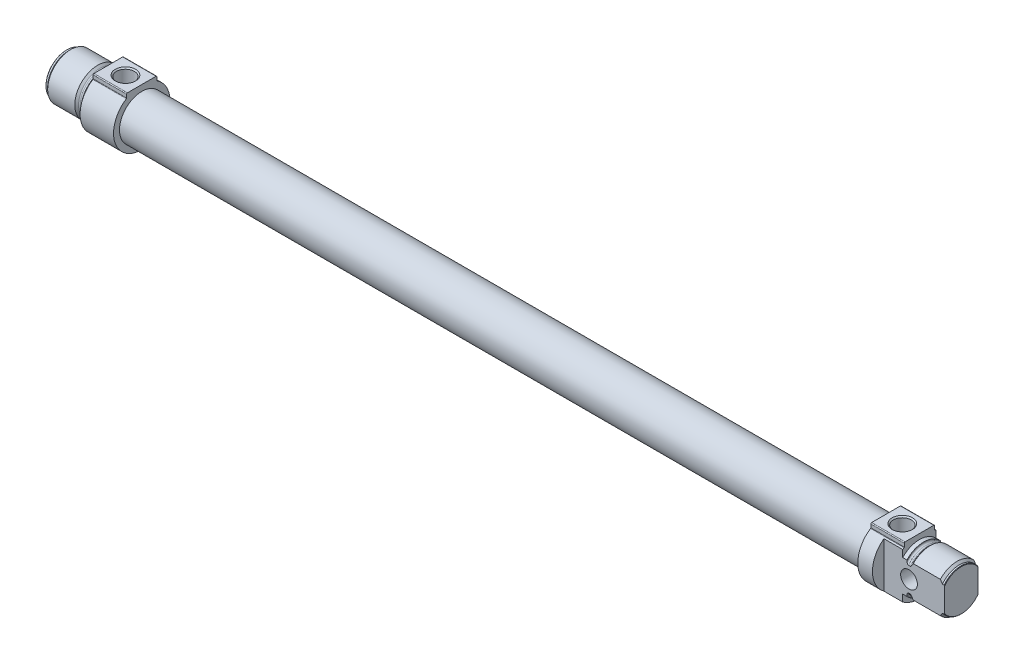
SolidWorks part; units mm, degrees
ref_plane "Ebene vorne" through (0, 0, 0) normal (0, 0, 1) x (1, 0, 0)
ref_plane "Ebene oben" through (0, 0, 0) normal (0, 1, 0) x (1, 0, 0)
ref_plane "Ebene rechts" through (0, 0, 0) normal (1, 0, 0) x (0, 0, -1)
sketch "Skizze1" plane through (0, 0, 0) normal (0, 0, 1) x (1, 0, 0)
  line L0 (0, 0) -> (0, 9.8)
  line L1 (0, 9.8) -> (0.2, 10)
  line L2 (0.2, 10) -> (1, 10)
  line L3 (1, 10) -> (2, 11)
  line L4 (2, 11) -> (14.95, 11)
  line L5 (14.95, 11) -> (15.8657, 10.0843)
  line L6 (16.4314, 9.85) -> (17.2, 9.85)
  line L7 (18, 10.65) -> (18, 11)
  line L8 (18, 11) -> (20, 11)
  line L9 (20, 11) -> (20, 0)
  line L10 (20, 0) -> (0, 0)
  line L11 (20, 0) -> (0, 0) construction
  arc A0 (15.8657, 10.0843) -> (16.4314, 9.85) centre (16.4314, 10.65) ccw
  arc A1 (17.2, 9.85) -> (18, 10.65) centre (17.2, 10.65) ccw
revolve "Rotation1" add sketch "Skizze1" angle 360 about L11 reverse direction yes
cosmetic thread "Gewindedarstellung1" parameters "D1"=13.87, "D2"=20.16
ref_plane "Ebene1" through (28.7, 0, 0) normal (1, 0, 0) x (0, 0, -1)
ref_plane "Ebene2" through (10.5, 0, 0) normal (1, 0, 0) x (0, 0, -1)
ref_plane "Ebene3" through (0, -14, 0) normal (0, 1, 0) x (1, 0, 0)
ref_plane "Ebene4" through (0, 13, 0) normal (0, 1, 0) x (1, 0, 0)
ref_plane "Ebene5" through (0, 0, 0) normal (0, 1, 0) x (1, 0, 0)
ref_plane "Ebene6" through (0, 0, 0) normal (0, 1, 0) x (1, 0, 0)
ref_plane "Ebene7" through (20, 0, 0) normal (1, 0, 0) x (0, 0, -1)
ref_plane "Ebene8" through (20, 0, 0) normal (1, 0, 0) x (0, 0, -1)
ref_plane "Ebene9" through (33, 0, 0) normal (1, 0, 0) x (0, 0, -1)
ref_plane "Ebene10" through (24.5, 0, 0) normal (1, 0, 0) x (0, 0, -1)
ref_plane "Ebene11" through (44.5, 0, 0) normal (1, 0, 0) x (0, 0, -1)
sketch "Skizze2" plane through (20, 0, 0) normal (1, 0, 0) x (0, 0, -1)
  line L0 (7.25, 11.5515) -> (7.25, 13.1)
  line L1 (6.85, 13.5) -> (-6.85, 13.5)
  line L2 (-7.25, 13.1) -> (-7.25, 11.5515)
  arc A0 (-7.3859, 11.3004) -> (7.3859, 11.3004) centre (0, 0) ccw
  arc A1 (7.3859, 11.3004) -> (7.25, 11.5515) centre (7.55, 11.5515) cw
  arc A2 (7.25, 13.1) -> (6.85, 13.5) centre (6.85, 13.1) ccw
  arc A3 (-6.85, 13.5) -> (-7.25, 13.1) centre (-6.85, 13.1) ccw
  arc A4 (-7.25, 11.5515) -> (-7.3859, 11.3004) centre (-7.55, 11.5515) cw
extrude "Aufsatz-Linear austragen1" add sketch "Skizze2" along normal blind 16
ref_plane "Ebene12" through (32.5, 0, 0) normal (1, 0, 0) x (0, 0, -1)
ref_plane "Ebene13" through (0, 0, 0) normal (0, 0, 1) x (1, 0, 0)
ref_plane "Ebene14" through (0, 0, -8.5) normal (0, 0, 1) x (1, 0, 0)
ref_plane "Ebene15" through (0, 0, 0) normal (0, 1, 0) x (1, 0, 0)
ref_plane "Ebene16" through (0, 6.9, 0) normal (0, 1, 0) x (1, 0, 0)
ref_plane "Ebene17" through (0, 0, -6.6) normal (0, 0, 1) x (1, 0, 0)
ref_plane "Ebene18" through (0, 0, 0) normal (0, 1, 0) x (1, 0, 0)
ref_plane "Ebene19" through (0, 6.9, 0) normal (0, 1, 0) x (1, 0, 0)
ref_plane "Ebene20" through (0, 7.8206, -1.379) normal (0, 0.9848, -0.1736) x (1, 0, 0)
ref_plane "Ebene21" through (0, 6.3434, -1.1185) normal (0, 0.9848, -0.1736) x (1, 0, 0)
sketch "Skizze3" plane through (0, 0, 0) normal (0, 0, 1) x (1, 0, 0)
  line L0 (36, 0) -> (36, 10.65)
  line L1 (36, 10.65) -> (392, 10.65)
  line L2 (392, 10.65) -> (392, 0)
  line L3 (392, 0) -> (36, 0)
  line L4 (392, 0) -> (36, 0) construction
revolve "Rotation2" add sketch "Skizze3" angle 360 about L4 reverse direction yes
ref_plane "Ebene22" through (392, 0, 0) normal (1, 0, 0) x (0, 0, -1)
sketch "Skizze4" plane through (392, 0, 0) normal (1, 0, 0) x (0, 0, -1)
  line L0 (7.25, 11.5515) -> (7.25, 13.1)
  line L1 (6.85, 13.5) -> (-6.85, 13.5)
  line L2 (-7.25, 13.1) -> (-7.25, 11.5515)
  arc A0 (-7.3859, 11.3004) -> (7.3859, 11.3004) centre (0, 0) ccw
  arc A1 (7.3859, 11.3004) -> (7.25, 11.5515) centre (7.55, 11.5515) cw
  arc A2 (7.25, 13.1) -> (6.85, 13.5) centre (6.85, 13.1) ccw
  arc A3 (-6.85, 13.5) -> (-7.25, 13.1) centre (-6.85, 13.1) ccw
  arc A4 (-7.25, 11.5515) -> (-7.3859, 11.3004) centre (-7.55, 11.5515) cw
extrude "Aufsatz-Linear austragen2" add sketch "Skizze4" along normal blind 16
ref_plane "Ebene23" through (395.8, 0, 0) normal (1, 0, 0) x (0, 0, -1)
ref_plane "Ebene24" through (395.5, 0, 0) normal (1, 0, 0) x (0, 0, -1)
ref_plane "Ebene25" through (0, 0, 6.6) normal (0, 0, 1) x (1, 0, 0)
ref_plane "Ebene26" through (0, 0, 0) normal (0, 1, 0) x (1, 0, 0)
ref_plane "Ebene27" through (0, 6.9, 0) normal (0, 1, 0) x (1, 0, 0)
ref_plane "Ebene28" through (0, 7.8206, 1.379) normal (0, 0.9848, 0.1736) x (1, 0, 0)
ref_plane "Ebene29" through (0, 6.3434, 1.1185) normal (0, 0.9848, 0.1736) x (1, 0, 0)
ref_plane "Ebene30" through (455, 0, 0) normal (1, 0, 0) x (0, 0, -1)
sketch "Skizze5" plane through (0, 0, 0) normal (0, 0, 1) x (1, 0, 0)
  line L0 (408, 0) -> (408, 11)
  line L1 (408, 11) -> (410, 11)
  line L2 (410, 11) -> (410, 10.65)
  line L3 (410.8, 9.85) -> (411.5686, 9.85)
  line L4 (412.1343, 10.0843) -> (413.05, 11)
  line L5 (413.05, 11) -> (426, 11)
  line L6 (426, 11) -> (427, 10)
  line L7 (427, 10) -> (427.8, 10)
  line L8 (427.8, 10) -> (428, 9.8)
  line L9 (428, 9.8) -> (428, 0)
  line L10 (428, 0) -> (408, 0)
  line L11 (428, 0) -> (408, 0) construction
  arc A0 (410, 10.65) -> (410.8, 9.85) centre (410.8, 10.65) ccw
  arc A1 (411.5686, 9.85) -> (412.1343, 10.0843) centre (411.5686, 10.65) ccw
revolve "Rotation3" add sketch "Skizze5" angle 360 about L11 reverse direction yes
cosmetic thread "Gewindedarstellung2" parameters "D1"=12.87, "D2"=20.16
ref_plane "Ebene31" through (442, 0, 0) normal (1, 0, 0) x (0, 0, -1)
ref_plane "Ebene32" through (450.5, 0, 0) normal (1, 0, 0) x (0, 0, -1)
ref_plane "Ebene33" through (430.5, 0, 0) normal (1, 0, 0) x (0, 0, -1)
sketch "Skizze6" plane through (0, 0, 0) normal (0, 1, 0) x (1, 0, 0)
  line L0 (399, 24) -> (399, 8)
  line L1 (399, 8) -> (428, 8)
  line L2 (428, 8) -> (428, -8)
  line L3 (428, -8) -> (399, -8)
  line L4 (399, -8) -> (399, -24)
  line L5 (399, -24) -> (444, -24)
  line L6 (444, -24) -> (444, 24)
  line L7 (444, 24) -> (399, 24)
extrude "Schnitt-Linear austragen1" cut sketch "Skizze6" along normal blind 13.5 and the other way blind 13.5
ref_plane "Ebene34" through (411, 0, 0) normal (1, 0, 0) x (0, 0, -1)
hole_wizard "Bohrung1" positions "Skizze8" profile "Skizze7" legacy
sketch "Skizze8" plane through (0, 0, -8) normal (0, 0, -1) x (-1, 0, 0)
  point P0 (-411, 0)
sketch "Skizze7" plane through (411, 0, -8) normal (1, 0, 0) x (0, 1, 0)
  line L0 (0, 0) -> (0, 16)
  line L1 (0, 16) -> (4, 16)
  line L2 (4, 16) -> (4, 0)
  line L3 (4, 0) -> (0, 0)
  line L4 (0, 110) -> (0, -10) construction
  dimension "Durchmesser" = 8
  dimension "Tiefe" = 16
hole_wizard "Bohrung2" positions "Skizze10" profile "Skizze9" legacy
sketch "Skizze10" plane through (0, 13.5, 0) normal (0, 1, 0) x (1, 0, 0)
  point P0 (28.2, 0)
sketch "Skizze9" plane through (28.2, 13.5, 0) normal (1, 0, 0) x (0, 0, 1)
  line L0 (0, 0) -> (0, 13.5)
  line L1 (0, 13.5) -> (4.283, 13.5)
  line L2 (4.283, 13.5) -> (4.283, 0.581)
  line L3 (4.283, 0.581) -> (4.864, 0)
  line L4 (4.864, 0) -> (0, 0)
  line L5 (0, -6.4453) -> (0, 115.525) construction
  line L6 (-4.283, 0.581) -> (-4.864, 0) construction
  dimension "Durchmesser" = 8.566
  dimension "Tiefe" = 13.5
  dimension "Senkwinkel1" = 90
  dimension "Senkdurchmesser3" = 9.728
cosmetic thread "Gewindedarstellung3" parameters "D1"=9.5, "D2"=9.728
hole_wizard "Bohrung3" positions "Skizze12" profile "Skizze11" legacy
sketch "Skizze12" plane through (0, 13.5, 0) normal (0, 1, 0) x (1, 0, 0)
  point P0 (399.8, 0)
sketch "Skizze11" plane through (399.8, 13.5, 0) normal (1, 0, 0) x (0, 0, 1)
  line L0 (0, 0) -> (0, 18.4728)
  line L1 (0, 18.4728) -> (4.283, 16)
  line L2 (4.283, 16) -> (4.283, 0.581)
  line L3 (4.283, 0.581) -> (4.864, 0)
  line L4 (4.864, 0) -> (0, 0)
  line L5 (0, -14.3089) -> (0, 102.4216) construction
  line L6 (0, 18.4728) -> (-4.283, 16) construction
  line L7 (-4.283, 0.581) -> (-4.864, 0) construction
  dimension "Durchmesser" = 8.566
  dimension "Tiefe" = 16
  dimension "Senkdurchmesser1" = 9.728
  dimension "Senkwinkel1" = 90
  dimension "Spitzenwinkel" = 120
cosmetic thread "Gewindedarstellung4" parameters "D1"=8, "D2"=9.728
sketch "Skizze13" plane through (0, 0, 0) normal (0, 0, 1) x (1, 0, 0)
  line L0 (-4, 0) -> (-4, 4)
  line L1 (-4, 4) -> (50.3, 4)
  line L2 (50.3, 4) -> (50.3, 10)
  line L3 (50.3, 10) -> (375.3, 10)
  line L4 (375.3, 10) -> (375.3, 0)
  line L5 (375.3, 0) -> (-4, 0)
  line L6 (375.3, 0) -> (-4, 0) construction
revolve "Schnitt-Rotation1" cut sketch "Skizze13" angle 360 about L6 reverse direction yes
ref_plane "Ebene35" through (-4, 0, 0) normal (1, 0, 0) x (0, 0, -1)
ref_plane "Ebene36" through (0, 13.5, 0) normal (0, 1, 0) x (1, 0, 0)
ref_plane "Ebene37" through (6.5, 0, 0) normal (1, 0, 0) x (0, 0, -1)
ref_plane "Ebene38" through (0, 0, 0) normal (1, 0, 0) x (0, 0, -1)
ref_plane "Ebene39" through (20, 0, 0) normal (1, 0, 0) x (0, 0, -1)
ref_plane "Ebene40" through (408, 0, 0) normal (1, 0, 0) x (0, 0, -1)
ref_plane "Ebene41" through (20, 0, 0) normal (1, 0, 0) x (0, 0, -1)
ref_plane "Ebene42" through (0, 13.5, 0) normal (0, 1, 0) x (1, 0, 0)
ref_plane "Ebene43" through (45.5, 0, 0) normal (1, 0, 0) x (0, 0, -1)
ref_plane "Ebene44" through (382.5, 0, 0) normal (1, 0, 0) x (0, 0, -1)
ref_plane "Ebene45" through (0, 0, 0) normal (0, 0, 1) x (1, 0, 0)
ref_plane "Ebene46" through (20, 0, 0) normal (1, 0, 0) x (0, 0, -1)
ref_plane "Ebene47" through (0, 13.5, 0) normal (0, 1, 0) x (1, 0, 0)
ref_plane "FDT_FRONT XY" through (20, 0, 0) normal (1, 0, 0) x (0, 0, -1)
ref_plane "FDT_FRONT XZ" through (0, 0, 0) normal (0, -1, 0) x (-1, 0, 0)
ref_plane "FDT_FRONT YZ" through (0, 0, 0) normal (0, 0, -1) x (-1, 0, 0)
ref_axis "FDT_FRONT X" through (20, 0, 80.9) along (0, 0, -1)
ref_axis "FDT_FRONT Y" through (20, -50, 0) along (0, 1, 0)
ref_axis "FDT_FRONT Z" through (80.9, 0, 0) along (-1, 0, 0)
sketch3d "FDT_FRONT"
  point P0 (20, 0, 0)
ref_plane "FDT_QSFRONT XY" through (0, 13.5, 0) normal (0, 1, 0) x (1, 0, 0)
ref_plane "FDT_QSFRONT XZ" through (28.2, 0, 0) normal (-1, 0, 0) x (0, 0, 1)
ref_plane "FDT_QSFRONT YZ" through (0, 0, 0) normal (0, 0, 1) x (1, 0, 0)
ref_axis "FDT_QSFRONT X" through (28.2, 13.5, -50) along (0, 0, 1)
ref_axis "FDT_QSFRONT Y" through (-80.9, 13.5, 0) along (1, 0, 0)
ref_axis "FDT_QSFRONT Z" through (28.2, 50, 0) along (0, -1, 0)
sketch3d "FDT_QSFRONT"
  point P0 (28.2, 13.5, 0)
ref_plane "FDT_QSREAR XY" through (0, 13.5, 0) normal (0, 1, 0) x (1, 0, 0)
ref_plane "FDT_QSREAR XZ" through (399.8, 0, 0) normal (-1, 0, 0) x (0, 0, 1)
ref_plane "FDT_QSREAR YZ" through (0, 0, 0) normal (0, 0, 1) x (1, 0, 0)
ref_axis "FDT_QSREAR X" through (399.8, 13.5, -50) along (0, 0, 1)
ref_axis "FDT_QSREAR Y" through (-80.9, 13.5, 0) along (1, 0, 0)
ref_axis "FDT_QSREAR Z" through (399.8, 50, 0) along (0, -1, 0)
sketch3d "FDT_QSREAR"
  point P0 (399.8, 13.5, 0)
ref_plane "FDT_REAR XY" through (408, 0, 0) normal (-1, 0, 0) x (0, 0, 1)
ref_plane "FDT_REAR XZ" through (0, 0, 0) normal (0, 1, 0) x (1, 0, 0)
ref_plane "FDT_REAR YZ" through (0, 0, 0) normal (0, 0, -1) x (-1, 0, 0)
ref_axis "FDT_REAR X" through (408, 0, 80.9) along (0, 0, -1)
ref_axis "FDT_REAR Y" through (408, 50, 0) along (0, -1, 0)
ref_axis "FDT_REAR Z" through (-80.9, 0, 0) along (1, 0, 0)
sketch3d "FDT_REAR"
  point P0 (408, 0, 0)
ref_plane "FDT_SMBR1 XY" through (45.5, 0, 0) normal (-1, 0, 0) x (0, 0, 1)
ref_plane "FDT_SMBR1 XZ" through (0, 0, 0) normal (0, -1, 0) x (-1, 0, 0)
ref_plane "FDT_SMBR1 YZ" through (0, 0, 0) normal (0, 0, 1) x (1, 0, 0)
ref_axis "FDT_SMBR1 X" through (45.5, 0, -80.9) along (0, 0, 1)
ref_axis "FDT_SMBR1 Y" through (45.5, -50, 0) along (0, 1, 0)
ref_axis "FDT_SMBR1 Z" through (-80.9, 0, 0) along (1, 0, 0)
sketch3d "FDT_SMBR1"
  point P0 (45.5, 0, 0)
ref_plane "FDT_SMBR2 XY" through (382.5, 0, 0) normal (-1, 0, 0) x (0, 0, 1)
ref_plane "FDT_SMBR2 XZ" through (0, 0, 0) normal (0, -1, 0) x (-1, 0, 0)
ref_plane "FDT_SMBR2 YZ" through (0, 0, 0) normal (0, 0, 1) x (1, 0, 0)
ref_axis "FDT_SMBR2 X" through (382.5, 0, -80.9) along (0, 0, 1)
ref_axis "FDT_SMBR2 Y" through (382.5, -50, 0) along (0, 1, 0)
ref_axis "FDT_SMBR2 Z" through (-80.9, 0, 0) along (1, 0, 0)
sketch3d "FDT_SMBR2"
  point P0 (382.5, 0, 0)
ref_plane "FDT_SWIVELAXIS XY" through (0, 0, 0) normal (0, 0, 1) x (1, 0, 0)
ref_plane "FDT_SWIVELAXIS XZ" through (0, 0, 0) normal (0, -1, 0) x (-1, 0, 0)
ref_plane "FDT_SWIVELAXIS YZ" through (411, 0, 0) normal (1, 0, 0) x (0, 0, -1)
ref_axis "FDT_SWIVELAXIS X" through (-80.9, 0, 0) along (1, 0, 0)
ref_axis "FDT_SWIVELAXIS Y" through (411, -50, 0) along (0, 1, 0)
ref_axis "FDT_SWIVELAXIS Z" through (411, 0, 80.9) along (0, 0, -1)
sketch3d "FDT_SWIVELAXIS"
  point P0 (411, 0, 0)
ref_plane "NUT XY" through (6.5, 0, 0) normal (1, 0, 0) x (0, 0, -1)
ref_plane "NUT XZ" through (0, 0, 0) normal (0, -1, 0) x (-1, 0, 0)
ref_plane "NUT YZ" through (0, 0, 0) normal (0, 0, -1) x (-1, 0, 0)
ref_axis "NUT X" through (6.5, 0, 80.9) along (0, 0, -1)
ref_axis "NUT Y" through (6.5, -50, 0) along (0, 1, 0)
ref_axis "NUT Z" through (80.9, 0, 0) along (-1, 0, 0)
sketch3d "NUT"
  point P0 (6.5, 0, 0)
ref_plane "ZR XY" through (0, 0, 0) normal (1, 0, 0) x (0, 0, -1)
ref_plane "ZR XZ" through (0, 0, 0) normal (0, -1, 0) x (-1, 0, 0)
ref_plane "ZR YZ" through (0, 0, 0) normal (0, 0, -1) x (-1, 0, 0)
ref_axis "ZR X" through (0, 0, 80.9) along (0, 0, -1)
ref_axis "ZR Y" through (0, -50, 0) along (0, 1, 0)
ref_axis "ZR Z" through (80.9, 0, 0) along (-1, 0, 0)
sketch3d "ZR"
  point P0 (0, 0, 0)
ref_plane "ZYL XY" through (20, 0, 0) normal (1, 0, 0) x (0, 0, -1)
ref_plane "ZYL XZ" through (0, 0, 0) normal (0, -1, 0) x (-1, 0, 0)
ref_plane "ZYL YZ" through (0, 0, 0) normal (0, 0, -1) x (-1, 0, 0)
ref_axis "ZYL X" through (20, 0, 80.9) along (0, 0, -1)
ref_axis "ZYL Y" through (20, -50, 0) along (0, 1, 0)
ref_axis "ZYL Z" through (80.9, 0, 0) along (-1, 0, 0)
sketch3d "ZYL"
  point P0 (20, 0, 0)
